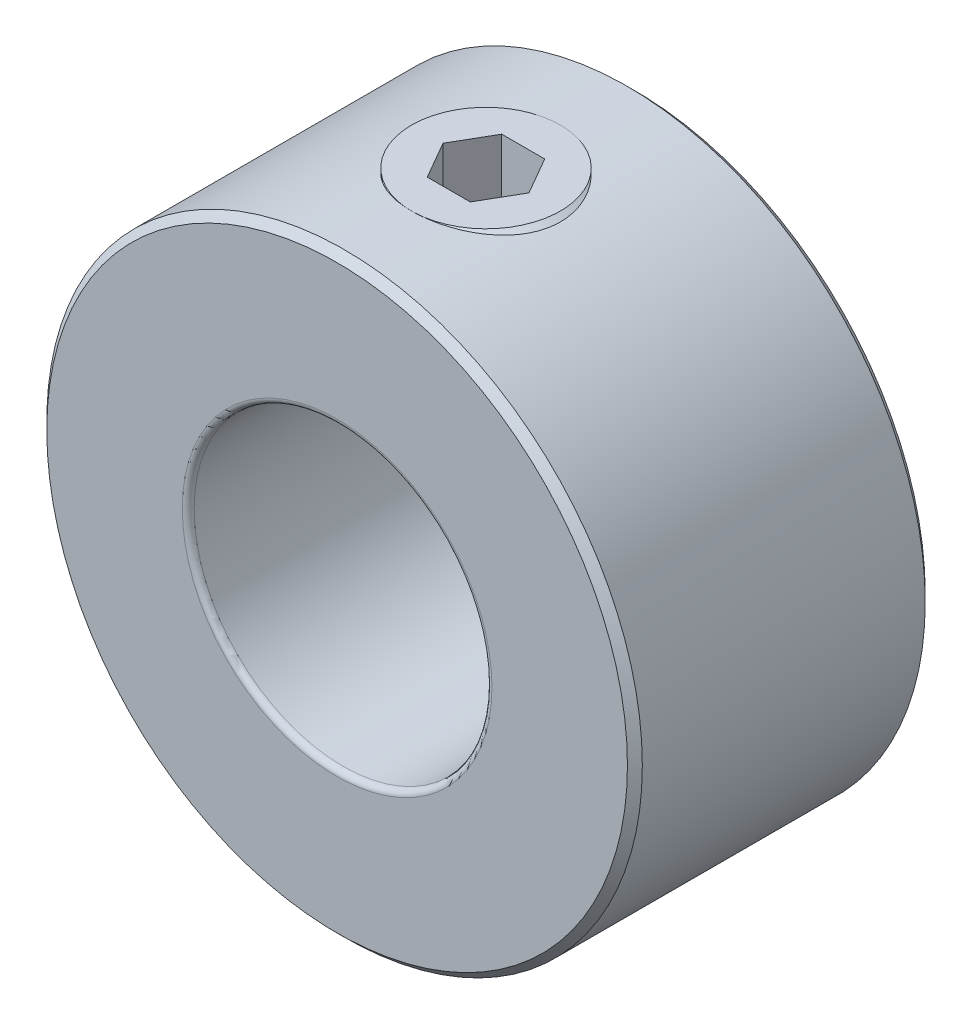
SolidWorks part; units mm, degrees
ref_plane "Front Plane" through (0, 0, 0) normal (0, 0, 1) x (1, 0, 0)
ref_plane "Top Plane" through (0, 0, 0) normal (0, 1, 0) x (1, 0, 0)
ref_plane "Right Plane" through (0, 0, 0) normal (1, 0, 0) x (0, 0, -1)
sketch "Sketch1" plane through (0, 0, 0) normal (0, 0, 1) x (1, 0, 0)
  line L0 (0, 10) -> (0, 0) construction
  line L1 (0, 0) -> (-7.0711, -7.0711) construction
  circle A0 centre (0, 0) radius 10
  circle A1 centre (0, 0) radius 5
  point P4 (10, 0)
  point P5 (0, 10)
  dimension "Bore Dia" = 10
  dimension "OD" = 20
  dimension "D1" = 135
extrude "Extrude1" add sketch "Sketch1" along normal blind 10
ref_plane "Plane1" through (0, 10, 0) normal (0, 1, 0) x (-1, 0, 0)
sketch "Sketch2" plane through (0, 10, 0) normal (0, 1, 0) x (-1, 0, 0)
  line L0 (0, 0) -> (0, 10) construction
  line L2 (10, 10) -> (-10, 10) construction
  circle A0 centre (0, 5) radius 2.5
  point P8 (0, 5)
  dimension "Set Screw Dia" = 5
extrude "Cut-Extrude1" cut sketch "Sketch2" against normal up to surface (10 mm away) up to plane "Top Plane"
ref_plane "Plane2" through (0, 0, 5) normal (0, 0, 1) x (1, 0, 0)
sketch "Sketch3" plane through (0, 0, 5) normal (0, 0, 1) x (1, 0, 0)
  line L0 (-2.25, 10) -> (-2.5, 9.8249)
  line L1 (0, 2.8231) -> (0, 10)
  line L3 (-2.5, 3.1301) -> (-2.5, 9.8249)
  line L4 (0, 10) -> (-2.25, 10)
  line L5 (0, 2) -> (0, 0) construction
  line L6 (-2.5, 9.8249) -> (0, 9.8249) construction
  line L7 (0, 2.8231) -> (-1.3699, 2)
  line L8 (-1.3699, 2) -> (-2.5, 3.1301)
  point P1 (-1.3699, 2)
  dimension "Screw Length" = 8
  dimension "D3" = 5
  dimension "D1" = 4.5
  dimension "D7" = 2.5
  dimension "D2" = 35
  dimension "D4" = 59
  dimension "D5" = 45
revolve "Revolve1" add sketch "Sketch3" angle 360 about L1
sketch "Sketch4" plane through (0, 10, 0) normal (0, 1, 0) x (0, 0, -1)
  line L0 (-5, 1.4434) -> (-5, -1.4434) construction
  line L1 (-5, 1.4434) -> (-6.25, 0.7217)
  line L2 (-6.25, 0.7217) -> (-6.25, -0.7217)
  line L3 (-6.25, -0.7217) -> (-5, -1.4434)
  line L4 (-5, -1.4434) -> (-3.75, -0.7217)
  line L5 (-3.75, -0.7217) -> (-3.75, 0.7217)
  line L6 (-3.75, 0.7217) -> (-5, 1.4434)
  circle A0 centre (-5, 0) radius 1.25 construction
  circle A1 centre (-5, 0) radius 1.4434 construction
  dimension "D1" = 2.8868
  dimension "Hex" = 2.5
extrude "Cut-Extrude2" cut sketch "Sketch4" against normal blind 2
fillet "Fillet1" radius 0.2 2 edges at (5, 0, 0) (5, 0, 10)
chamfer "Chamfer1" distance 0.25 angle 45 2 edges at (10, 0, 10) (10, 0, 0)
sketch "Sketch5" plane through (0, 10, 0) normal (0, 1, 0) x (1, 0, 0)
  circle A0 centre (0, -5) radius 2.5 construction
  circle A1 centre (0, -5) radius 2.5
curve "Helix/Spiral1" pitch 0.8 height 8 radius 2.5 centre (0, 10, 5) axis (0, -1, 0) start towards (-1, 0, 0) parameters "Pitch"=0.8
ref_plane "Plane3" through (0, 0, 5) normal (0, 0, 1) x (1, 0, 0)
sketch "Sketch9" plane through (0, 0, 5) normal (0, 0, 1) x (1, 0, 0)
  line L0 (-2.5, 10) -> (-2.5, 10.7)
  line L1 (-2.5, 10.7) -> (-1.9804, 10.4)
  line L2 (-1.9804, 10.4) -> (-1.9804, 10.3)
  line L3 (-1.9804, 10.3) -> (-2.5, 10)
  line L4 (-2.5, 10.35) -> (-1.9804, 10.35) construction
  line L5 (-2.2402, 10.15) -> (-2.2402, 10.55) construction
  dimension "D1" = 0.1
  dimension "D2" = 0.4
  dimension "D3" = 60
sweep "Cut-Sweep2" cut profiles "Sketch9" path "Helix/Spiral1" align with end faces yes
sketch "Sketch10" plane through (0, 10, 0) normal (0, 1, 0) x (1, 0, 0)
  line L0 (-0.7217, -3.75) -> (-1.4434, -5) construction
  line L1 (-1.4434, -5) -> (-0.7217, -6.25) construction
  line L2 (-0.7217, -6.25) -> (0.7217, -6.25) construction
  line L3 (0.7217, -6.25) -> (1.4434, -5) construction
  line L4 (1.4434, -5) -> (0.7217, -3.75) construction
  line L5 (0.7217, -3.75) -> (-0.7217, -3.75) construction
  line L6 (-0.7217, -3.75) -> (-1.4434, -5)
  line L7 (-1.4434, -5) -> (-0.7217, -6.25)
  line L8 (-0.7217, -6.25) -> (0.7217, -6.25)
  line L9 (0.7217, -6.25) -> (1.4434, -5)
  line L10 (1.4434, -5) -> (0.7217, -3.75)
  line L11 (0.7217, -3.75) -> (-0.7217, -3.75)
  circle A0 centre (0, -5) radius 2.5 construction
  circle A1 centre (0, -5) radius 2.5
extrude "Boss-Extrude1" add sketch "Sketch10" against normal through all draft 60
ref_plane "Contact Plane 1" through (0, 0, 10) normal (0, 0, 1) x (1, 0, 0)
ref_plane "Contact Plane 2" through (0, 0, 0) normal (0, 0, -1) x (-1, 0, 0)
ref_plane "Contact Plane 3" through (0, 2, 0) normal (0, -1, 0) x (-1, 0, 0)
ref_axis "Central Axis 1" through (0, 0, 9.8) along (0, 0, -1)
equation "\"D1@Fillet1\" = \"OD@Sketch1\"*.01"
equation "\"D1@Cut-Extrude2\" = \"Hex@Sketch4\"*.8"
equation "\"D3@Sketch3\"=\"Set Screw Dia@Sketch2\""
equation "\"D1@Sketch3\"=\"Set Screw Dia@Sketch2\"*.9"
equation "\"D3@Helix/Spiral1\"=\"Screw Length@Sketch3\""
equation "\"D1@Sketch9\"=\"Pitch@Helix/Spiral1\"*.125"
equation "\"D2@Sketch9\"=\"Pitch@Helix/Spiral1\"*.50"
